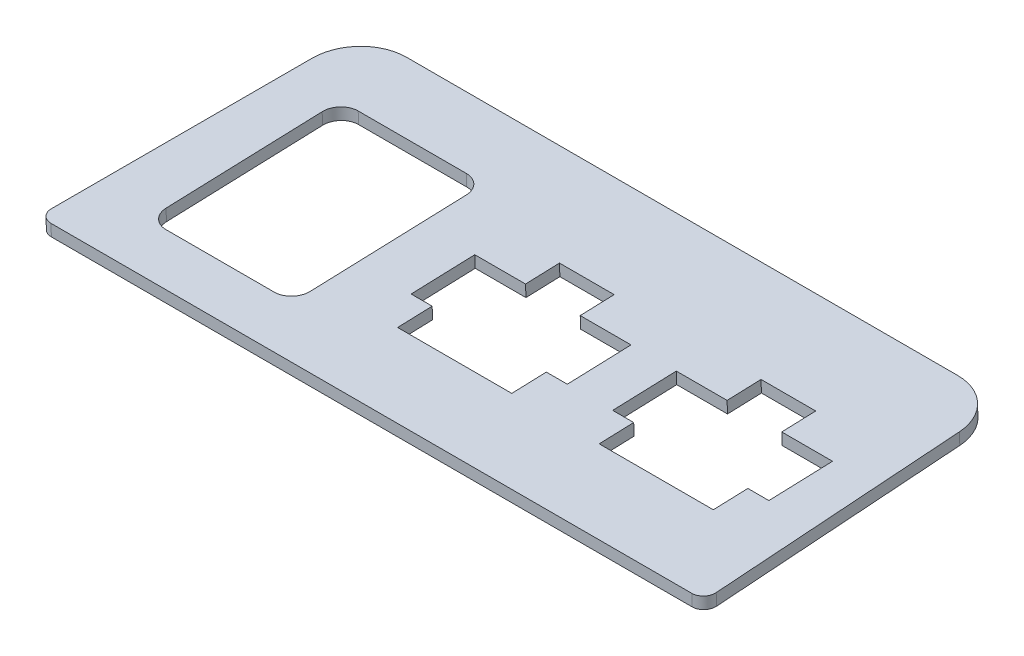
SolidWorks part; units mm, degrees
ref_plane "Front Plane" through (0, 0, 0) normal (0, 0, 1) x (1, 0, 0)
ref_plane "Top Plane" through (0, 0, 0) normal (0, 1, 0) x (1, 0, 0)
ref_plane "Right Plane" through (0, 0, 0) normal (1, 0, 0) x (0, 0, -1)
sketch "Sketch1" plane through (0, -69.2407, -2.4179) normal (0, 0.9994, 0.0349) x (1, 0, 0)
  line L4 (-46.6585, 44.5513) -> (46.6585, 44.5513) construction
  line L8 (-55.4003, -4.2069) -> (55.4003, -4.2069)
  line L9 (55.4003, -4.2069) -> (53.8625, 39.8305)
  line L10 (45.8674, 47.5513) -> (-45.8674, 47.5513)
  line L11 (-53.8625, 39.8305) -> (-55.4003, -4.2069)
  arc A4 (53.8625, 39.8305) -> (45.8674, 47.5513) centre (45.8674, 39.5513) ccw
  arc A5 (-45.8674, 47.5513) -> (-53.8625, 39.8305) centre (-45.8674, 39.5513) ccw
  dimension "D4" = 8
  dimension "D3" = 3
extrude "Boss-Extrude1" add sketch "Sketch1" along normal blind 2
sketch "Sketch2" plane through (0, -69.2407, -2.4179) normal (0, -0.9994, -0.0349) x (1, 0, 0)
  line L0 (-4.05, -25.5222) -> (-4.05, -31.1722)
  line L1 (-42.5472, -4.1722) -> (-24.5472, -4.1722)
  line L2 (-45.5472, -7.1722) -> (-45.5472, -33.1722)
  line L3 (-42.5472, -36.1722) -> (-24.5472, -36.1722)
  line L4 (-21.5472, -7.1722) -> (-21.5472, -33.1722)
  line L5 (-12.5, -14.9222) -> (-9, -14.9222)
  line L6 (-12.5, -14.9222) -> (-12.5, -25.5222)
  line L7 (-12.5, -25.5222) -> (-4.05, -25.5222)
  line L8 (13.5, -14.9222) -> (13.5, -25.5222)
  line L9 (-9, -9.1722) -> (10, -9.1722)
  line L10 (-9, -9.1722) -> (-9, -14.9222)
  line L11 (-4.05, -31.1722) -> (5.05, -31.1722)
  line L12 (10, -9.1722) -> (10, -14.9222)
  line L13 (10, -14.9222) -> (13.5, -14.9222)
  line L14 (5.05, -25.5222) -> (5.05, -31.1722)
  line L15 (5.05, -25.5222) -> (13.5, -25.5222)
  line L16 (-13, -6.6722) -> (14, -33.6722) construction
  line L17 (-13, -6.6722) -> (14, -6.6722) construction
  line L18 (-13, -6.6722) -> (-13, -33.6722) construction
  line L19 (-13, -33.6722) -> (14, -33.6722) construction
  line L20 (14, -6.6722) -> (14, -33.6722) construction
  line L21 (17.2736, 3.7502) -> (17.2736, -36.664) construction
  line L22 (47.0472, -20.2222) -> (21.0472, -20.2222) construction
  line L23 (34.0472, -9.1722) -> (34.0472, -31.1722) construction
  line L24 (20.5472, -6.6722) -> (20.5472, -33.6722) construction
  line L25 (47.5472, -33.6722) -> (20.5472, -33.6722) construction
  line L26 (47.5472, -6.6722) -> (47.5472, -33.6722) construction
  line L27 (47.5472, -6.6722) -> (20.5472, -6.6722) construction
  line L28 (-47.5472, -20.1722) -> (-45.5472, -20.1722) construction
  line L29 (-47.5472, -2.1722) -> (-19.5472, -2.1722) construction
  line L30 (-47.5472, -2.1722) -> (-47.5472, -38.1722) construction
  line L31 (-47.5472, -38.1722) -> (-19.5472, -38.1722) construction
  line L32 (-19.5472, -2.1722) -> (-19.5472, -38.1722) construction
  line L33 (-33.5472, -4.1722) -> (-33.5472, -2.1722) construction
  line L34 (0.5, -9.1722) -> (0.5, -31.1722) construction
  line L35 (-12.5, -20.2222) -> (13.5, -20.2222) construction
  line L36 (47.5472, -6.6722) -> (20.5472, -33.6722) construction
  line L37 (29.4972, -25.5222) -> (21.0472, -25.5222)
  line L38 (29.4972, -25.5222) -> (29.4972, -31.1722)
  line L39 (24.5472, -14.9222) -> (21.0472, -14.9222)
  line L40 (24.5472, -9.1722) -> (24.5472, -14.9222)
  line L41 (38.5972, -31.1722) -> (29.4972, -31.1722)
  line L42 (43.5472, -9.1722) -> (43.5472, -14.9222)
  line L43 (43.5472, -9.1722) -> (24.5472, -9.1722)
  line L44 (21.0472, -14.9222) -> (21.0472, -25.5222)
  line L45 (47.0472, -25.5222) -> (38.5972, -25.5222)
  line L46 (47.0472, -14.9222) -> (47.0472, -25.5222)
  line L47 (47.0472, -14.9222) -> (43.5472, -14.9222)
  line L48 (38.5972, -25.5222) -> (38.5972, -31.1722)
  line L49 (20.5472, -20.1722) -> (14, -20.1722) construction
  line L50 (-55.4003, 4.2069) -> (55.4003, 4.2069) construction
  line L51 (47.5472, -20.1722) -> (51.5472, -20.1722) construction
  line L52 (55.4003, 4.2069) -> (53.8625, -39.8305) construction
  line L53 (-46.6585, -44.5513) -> (46.6585, -44.5513) construction
  line L54 (-13, -20.1722) -> (-19.5472, -20.1722) construction
  line L55 (-33.5472, -2.1722) -> (-33.5472, 4.2069) construction
  line L56 (-33.5472, -38.1722) -> (-33.5472, -44.5513) construction
  line L57 (-53.8625, -39.8305) -> (-55.4003, 4.2069) construction
  line L58 (-47.5472, -20.1722) -> (-51.5472, -20.1722) construction
  arc A0 (-45.5472, -33.1722) -> (-42.5472, -36.1722) centre (-42.5472, -33.1722) ccw
  arc A1 (-24.5472, -36.1722) -> (-21.5472, -33.1722) centre (-24.5472, -33.1722) ccw
  arc A2 (-24.5472, -4.1722) -> (-21.5472, -7.1722) centre (-24.5472, -7.1722) cw
  arc A3 (-42.5472, -4.1722) -> (-45.5472, -7.1722) centre (-42.5472, -7.1722) ccw
  point P28 (0.5, -20.1722)
  point P63 (34.0472, -20.1722)
  dimension "D1" = 3
  dimension "D2" = 32
  dimension "D3" = 24
  dimension "D4" = 28
  dimension "D5" = 36
  dimension "D6" = 26
  dimension "D7" = 22
  dimension "D8" = 10.6
  dimension "D9" = 19
  dimension "D10" = 9.1
  dimension "D11" = 5.75
  dimension "D12" = 27
  dimension "D13" = 27
  dimension "D14" = 4
  dimension "D15" = 3
  dimension "D16" = 3
extrude "Cut-Extrude1" cut sketch "Sketch2" against normal up to next
fillet "Fillet1" radius 2 2 edges at (-55.4003, -68.3881, 1.8213) (55.4003, -68.3881, 1.8213)
